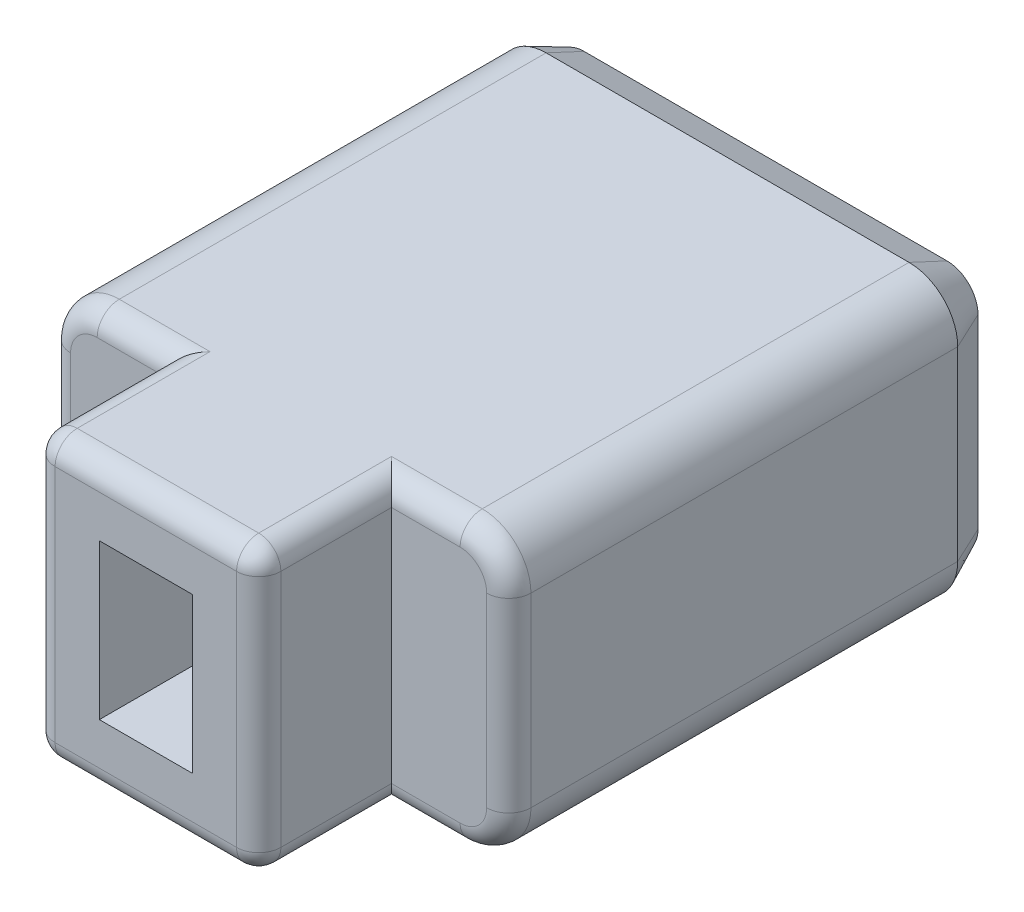
SolidWorks part; units mm, degrees
ref_plane "Plan de face" through (0, 0, 0) normal (0, 0, 1) x (1, 0, 0)
ref_plane "Plan de dessus" through (0, 0, 0) normal (0, 1, 0) x (1, 0, 0)
ref_plane "Plan de droite" through (0, 0, 0) normal (1, 0, 0) x (0, 0, -1)
sketch "Esquisse2" plane through (0, 0, 0) normal (0, 0, 1) x (1, 0, 0)
  line L1 (1.1, 0) -> (9.3, 0)
  line L2 (0, 1.1) -> (0, 5.3)
  line L3 (1.1, 6.4) -> (9.3, 6.4)
  line L4 (10.4, 1.1) -> (10.4, 5.3)
  arc A0 (9.3, 6.4) -> (10.4, 5.3) centre (9.3, 5.3) cw
  arc A1 (9.3, 0) -> (10.4, 1.1) centre (9.3, 1.1) ccw
  arc A2 (1.1, 0) -> (0, 1.1) centre (1.1, 1.1) cw
  arc A3 (0, 5.3) -> (1.1, 6.4) centre (1.1, 5.3) cw
  point P7 (10.4, 6.4)
  point P12 (0, 0)
  point P15 (0, 6.4)
  dimension "D3" = 1.1
  dimension "D1" = 10.4
  dimension "D2" = 6.4
extrude "Boss.-Extru.1" add sketch "Esquisse2" along normal blind 14
sketch "Esquisse3" plane through (0, 0, 14) normal (0, 0, 1) x (1, 0, 0)
  line L0 (0, 5.3) -> (0, 1.1) construction
  line L1 (4.15, 4.95) -> (6.25, 4.95)
  line L2 (4.15, 4.95) -> (4.15, 1.45)
  line L3 (4.15, 1.45) -> (6.25, 1.45)
  line L4 (6.25, 4.95) -> (6.25, 1.45)
  line L5 (10.4, 1.1) -> (10.4, 5.3) construction
  line L6 (9.3, 6.4) -> (1.1, 6.4) construction
  line L7 (1.1, 0) -> (9.3, 0) construction
  dimension "D1" = 2.1
  dimension "D2" = 3.5
  dimension "D3" = 4.15
  dimension "D4" = 4.15
  dimension "D5" = 1.45
  dimension "D6" = 1.45
extrude "Enlèv. mat.-Extru.1" cut sketch "Esquisse3" against normal blind 3
sketch "Esquisse4" plane through (0, 0, 14) normal (0, 0, 1) x (1, 0, 0)
  line L0 (2.65, 6.4) -> (2.65, 0)
  line L1 (9.3, 6.4) -> (1.1, 6.4) construction
  line L2 (1.1, 0) -> (9.3, 0) construction
  line L3 (2.65, 0) -> (7.75, 0)
  line L4 (7.75, 0) -> (7.75, 6.4)
  line L5 (7.75, 6.4) -> (2.65, 6.4)
  line L6 (4.15, 4.95) -> (4.15, 1.45) construction
  line L7 (6.25, 1.45) -> (6.25, 4.95) construction
  dimension "D1" = 1.5
  dimension "D2" = 1.5
extrude "Enlèv. mat.-Extru.2" cut sketch "Esquisse4" against normal blind 3 flip side to cut
fillet "Congé1" radius 0.5 18 edges at (8.525, 0, 11) (10.0778, 0.3222, 11) (10.4, 3.2, 11) (10.0778, 6.0778, 11) (1.875, 6.4, 11) (0.3222, 6.0778, 11) (1.875, 0, 11) (0.3222, 0.3222, 11) (7.75, 6.4, 12.5) (2.65, 6.4, 12.5) (7.75, 0, 12.5) (2.65, 0, 12.5) (2.65, 3.2, 14) (5.2, 6.4, 14) (7.75, 3.2, 14) (5.2, 0, 14) (8.525, 6.4, 11) (0, 3.2, 11)
chamfer "Chanfrein1" distance 0.4 angle 65 8 edges at (5.2, 0, 0) (10.0778, 0.3222, 0) (0.3222, 0.3222, 0) (10.4, 3.2, 0) (0, 3.2, 0) (10.0778, 6.0778, 0) (0.3222, 6.0778, 0) (5.2, 6.4, 0) first distance on face at (5.2, 3.2, 0)
sketch "Esquisse5" plane through (0, 0, 0) normal (0, 0, -1) x (-1, 0, 0)
  line L0 (-0.4, 5.3) -> (-10, 5.3) construction
  arc A0 (-9.3, 6) -> (-10, 5.3) centre (-9.3, 5.3) ccw construction
  text T0 "2" font "Century Gothic" height 4
extrude "Enlèv. mat.-Extru.3" cut sketch "Esquisse5" against normal blind 0.3
extrude "Boss.-Extru.2" add sketch "Esquisse5<2>" along normal blind 0.3 separate body
sketch "Esquisse5<2>" plane through (0, 0, 0) normal (0, 0, -1) x (-1, 0, 0) same geometry as "Esquisse5"
